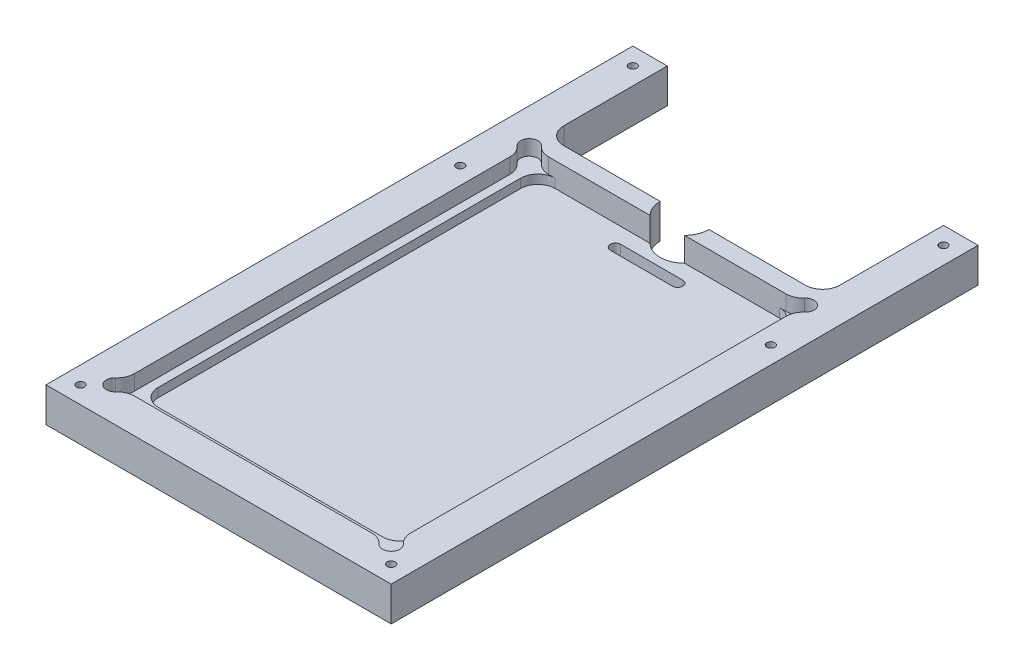
SolidWorks part; units mm, degrees
ref_plane "Front" through (0, 0, 0) normal (0, 0, 1) x (1, 0, 0)
ref_plane "Top" through (0, 0, 0) normal (0, 1, 0) x (1, 0, 0)
ref_plane "Right" through (0, 0, 0) normal (1, 0, 0) x (0, 0, -1)
sketch "Sketch2" plane through (0, 0, 0) normal (0, 1, 0) x (1, 0, 0)
  line L1 (0, 0) -> (127, 0)
  line L2 (0, 0) -> (0, 215.9)
  line L3 (0, 215.9) -> (127, 215.9)
  line L4 (127, 0) -> (127, 215.9)
  dimension "D1" = 215.9
  dimension "D2" = 127
extrude "Boss-Extrude1" add sketch "Sketch2" along normal blind 12.7
sketch "Sketch5" plane through (0, 12.7, 0) normal (0, 1, 0) x (1, 0, 0)
  line L0 (0, 215.9) -> (0, 0) construction
  line L1 (12.7, 12.7) -> (114.3, 12.7)
  line L2 (12.7, 12.7) -> (12.7, 165.1)
  line L3 (12.7, 165.1) -> (114.3, 165.1)
  line L4 (114.3, 12.7) -> (114.3, 165.1)
  line L5 (127, 0) -> (127, 215.9) construction
  line L6 (0, 0) -> (127, 0) construction
  line L7 (127, 215.9) -> (0, 215.9) construction
  dimension "D1" = 12.7
  dimension "D2" = 12.7
  dimension "D3" = 12.7
  dimension "D4" = 50.8
extrude "Cut-Extrude3" cut sketch "Sketch5" against normal blind 5.588
sketch "Sketch6" plane through (0, 12.7, 0) normal (0, 1, 0) x (1, 0, 0)
  line L0 (127, 215.9) -> (0, 215.9) construction
  line L1 (12.7, 215.9) -> (114.3, 215.9)
  line L2 (12.7, 215.9) -> (12.7, 171.45)
  line L3 (12.7, 171.45) -> (114.3, 171.45)
  line L4 (114.3, 215.9) -> (114.3, 171.45)
  line L5 (0, 215.9) -> (0, 0) construction
  line L6 (127, 0) -> (127, 215.9) construction
  line L7 (114.3, 165.1) -> (12.7, 165.1) construction
  dimension "D1" = 12.7
  dimension "D2" = 12.7
  dimension "D3" = 6.35
extrude "Cut-Extrude4" cut sketch "Sketch6" against normal through all
sketch "Sketch8" plane through (0, 12.7, 0) normal (0, 1, 0) x (1, 0, 0)
  line L1 (63.5, 171.45) -> (63.5, 165.1) construction
  line L2 (12.7, 171.45) -> (114.3, 171.45) construction
  line L3 (114.3, 165.1) -> (12.7, 165.1) construction
  line L4 (63.5, 165.1) -> (69.85, 165.1) construction
  circle A1 centre (63.5, 171.45) radius 8.9803
  dimension "D1" = 6.35
extrude "Cut-Extrude6" cut sketch "Sketch8" against normal through all
sketch "Sketch9" plane through (0, 7.112, 0) normal (0, 1, 0) x (1, 0, 0)
  line L0 (57.15, 165.1) -> (12.7, 165.1) construction
  line L1 (15.875, 165.1) -> (111.125, 165.1)
  line L2 (15.875, 165.1) -> (15.875, 19.05)
  line L3 (15.875, 19.05) -> (111.125, 19.05)
  line L4 (111.125, 165.1) -> (111.125, 19.05)
  line L5 (12.7, 165.1) -> (12.7, 12.7) construction
  line L6 (114.3, 12.7) -> (114.3, 165.1) construction
  line L7 (12.7, 12.7) -> (114.3, 12.7) construction
  dimension "D1" = 3.175
  dimension "D2" = 3.175
  dimension "D3" = 6.35
extrude "Cut-Extrude7" cut sketch "Sketch9" against normal blind 3.302
sketch "Sketch11" plane through (0, 3.81, 0) normal (0, 1, 0) x (1, 0, 0)
  line L0 (74.93, 157.48) -> (52.07, 157.48) construction
  line L1 (74.93, 155.575) -> (52.07, 155.575)
  line L2 (74.93, 159.385) -> (52.07, 159.385)
  line L3 (57.15, 165.1) -> (15.875, 165.1) construction
  line L4 (12.7, 165.1) -> (12.7, 12.7) construction
  arc A0 (74.93, 155.575) -> (74.93, 159.385) centre (74.93, 157.48) ccw
  arc A1 (52.07, 159.385) -> (52.07, 155.575) centre (52.07, 157.48) ccw
  point P2 (63.5, 157.48)
  dimension "D2" = 1.905
  dimension "D1" = 22.86
  dimension "D3" = 7.62
  dimension "D4" = 39.37
extrude "Cut-Extrude8" cut sketch "Sketch11" against normal blind 3.81
hole_wizard "#32 (0.116) Diameter Hole1" positions "Sketch12" profile "Sketch13" hole size "#32" standard "ANSI Inch" end condition through all
sketch "Sketch12" plane through (0, 12.7, 0) normal (0, 1, 0) x (1, 0, 0)
  line L0 (0, 215.9) -> (0, 0) construction
  line L1 (12.7, 215.9) -> (0, 215.9) construction
  line L2 (63.5, 0) -> (63.5, 236.2305) construction
  line L3 (0, 0) -> (127, 0) construction
  line L5 (0, 107.95) -> (127, 107.95) construction
  line L6 (127, 0) -> (127, 215.9) construction
  point P0 (6.35, 209.55)
  point P20 (120.65, 209.55)
  point P22 (120.65, 6.35)
  point P23 (6.35, 6.35)
  point P24 (6.35, 209.55)
  point P26 (120.65, 209.55)
  point P34 (6.35, 146.05)
  point P35 (120.65, 146.05)
  dimension "D1" = 6.35
  dimension "D2" = 6.35
  dimension "D3" = 2
sketch "Sketch13" plane through (6.35, 12.7, -209.55) normal (1, 0, 0) x (0, 0, 1)
  line L0 (0, 0) -> (0, 12.7)
  line L1 (0, 12.7) -> (1.4732, 12.7)
  line L2 (1.4732, 12.7) -> (1.4732, 0)
  line L5 (1.4732, 0) -> (0, 0)
  line L11 (0, -6.35) -> (0, 107.95) construction
  dimension "Thru Hole Dia." = 2.9464
  dimension "Thru Hole Depth" = 12.7
sketch "Sketch18" plane through (0, 12.7, 0) normal (0, 1, 0) x (1, 0, 0)
  circle A0 centre (12.7, 165.1) radius 3.175
  circle A1 centre (114.3, 165.1) radius 3.175
  circle A2 centre (114.3, 12.7) radius 3.175
  circle A3 centre (12.7, 12.7) radius 3.175
  dimension "D1" = 6.35
  dimension "D3" = 2
  dimension "D2" = 2
extrude "Cut-Extrude9" cut sketch "Sketch18" against normal blind 5.588
fillet "Fillet5" radius 6.35 8 edges at (12.7, 9.906, -161.925) (15.875, 9.906, -165.1) (12.7, 9.906, -15.875) (15.875, 9.906, -12.7) (111.125, 9.906, -12.7) (114.3, 9.906, -15.875) (114.3, 9.906, -161.925) (111.125, 9.906, -165.1)
fillet "Fillet7" radius 6.35 2 edges at (114.3, 6.35, -171.45) (12.7, 6.35, -171.45)
fillet "Fillet8" radius 6.35 2 edges at (111.125, 5.461, -19.05) (15.875, 5.461, -19.05)
fillet "Fillet10" radius 6.35 1 edges at (111.125, 5.461, -165.1) type face fillet first side face at (111.125, 5.461, -95.25) second side face at (96.0585, 7.874, -165.1)
fillet "Fillet11" radius 6.35 1 edges at (15.875, 5.461, -165.1) type face fillet first side face at (30.9415, 7.874, -165.1) second side face at (15.875, 5.461, -95.25)
